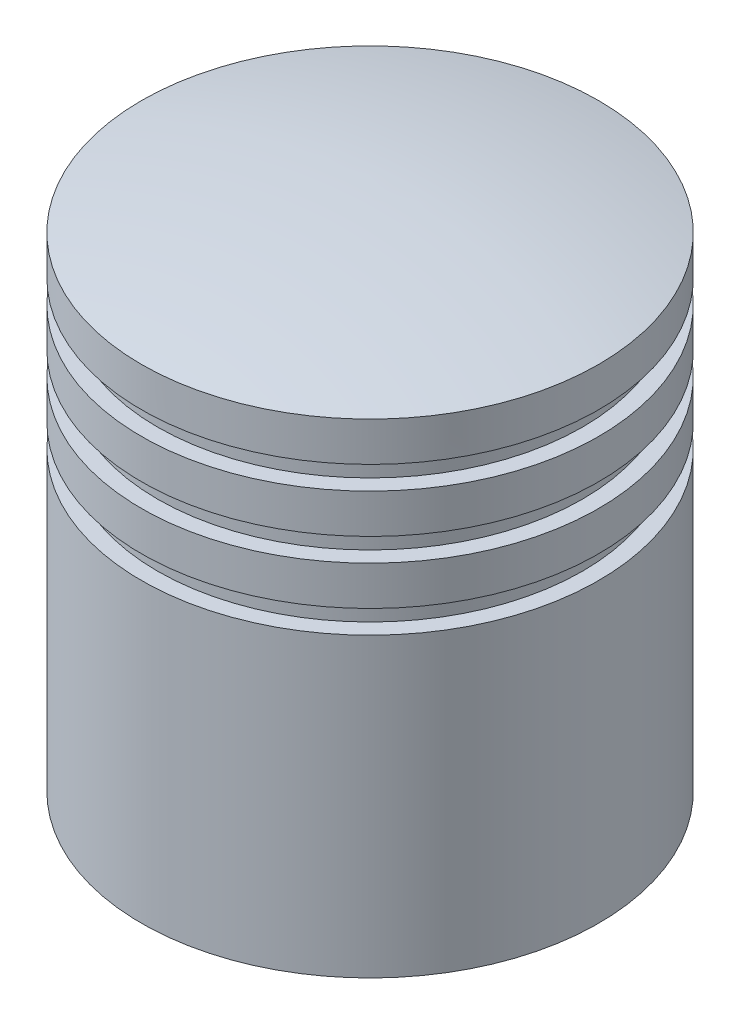
SolidWorks part; units mm, degrees
ref_plane "Front Plane" through (0, 0, 0) normal (0, 0, 1) x (1, 0, 0)
ref_plane "Top Plane" through (0, 0, 0) normal (0, 1, 0) x (1, 0, 0)
ref_plane "Right Plane" through (0, 0, 0) normal (1, 0, 0) x (0, 0, -1)
sketch "Sketch1" plane through (0, 0, 0) normal (0, 1, 0) x (1, 0, 0)
  circle A0 centre (0, 0) radius 42.5
  dimension "D1" = 85
extrude "Boss-Extrude1" add sketch "Sketch1" along normal blind 90
sketch "Sketch2" plane through (0, 90, 0) normal (0, 1, 0) x (1, 0, 0)
  circle A0 centre (0, 0) radius 39.5
  dimension "D1" = 79
extrude "Cut-Extrude2" cut sketch "Sketch2" against normal blind 4.3 from offset 7.3 flip side to cut offset against normal yes
pattern_linear "LPattern1" count 3 spacing 11.6 along (0, -1, 0) of "Cut-Extrude2"
sketch "Sketch3" plane through (0, 0, 0) normal (0, -1, 0) x (1, 0, 0)
  circle A0 centre (0, 0) radius 38
  dimension "D1" = 76
extrude "Cut-Extrude3" cut sketch "Sketch3" against normal blind 85
dome "Dome1" faces to dome 1 distance 5 reverse direction no elliptical dome no face at (0, 90, 42.5) parameters "D1"=5
